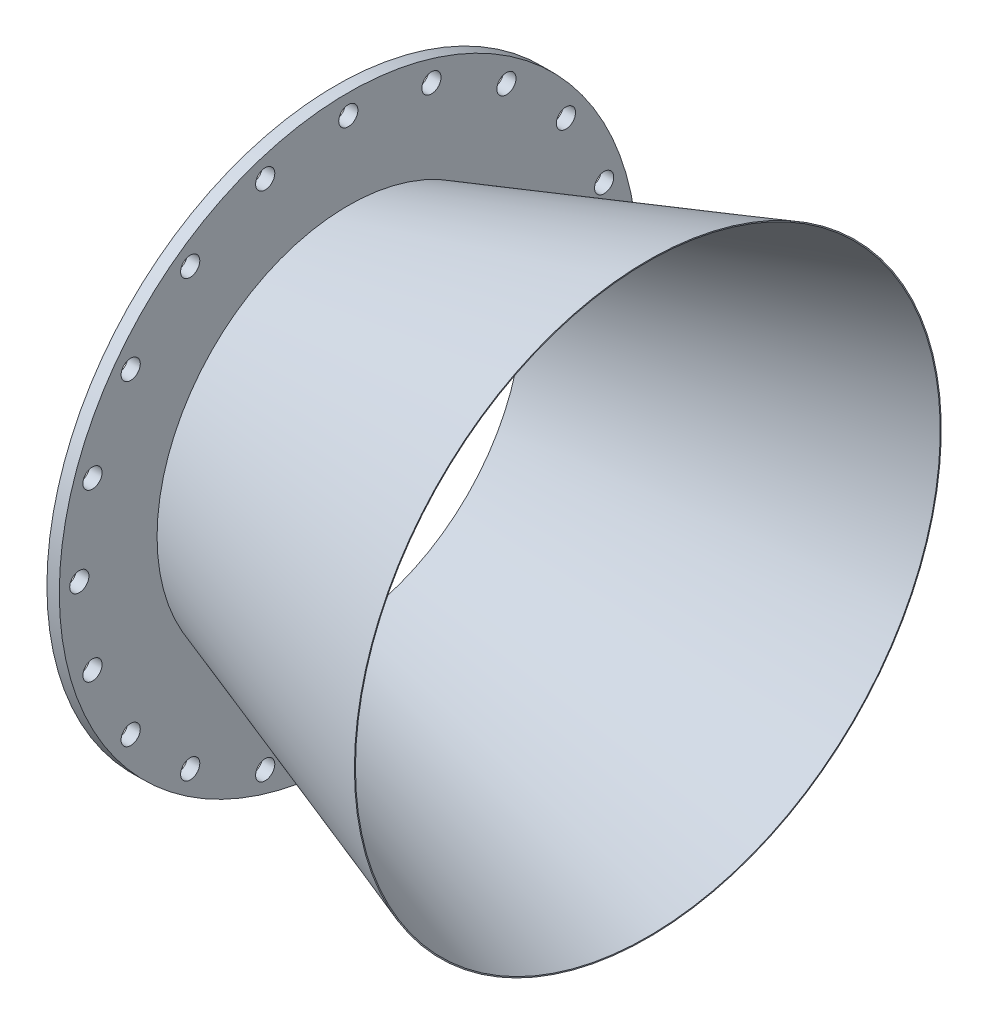
SolidWorks part; units mm, degrees
material "Tungsten"
ref_plane "Front Plane" through (0, 0, 0) normal (0, 0, 1) x (1, 0, 0)
ref_plane "Top Plane" through (0, 0, 0) normal (0, 1, 0) x (1, 0, 0)
ref_plane "Right Plane" through (0, 0, 0) normal (1, 0, 0) x (0, 0, -1)
sketch "Sketch1" plane through (0, 0, 0) normal (0, 0, 1) x (1, 0, 0)
  line L0 (0, 0) -> (0, 47.6758) construction
  line L1 (0, 0) -> (79.9592, 0) construction
  line L2 (79.9592, 0) -> (79.9592, 74.9554) construction
  line L3 (0, 47.6758) -> (45.8899, 47.6758) construction
  line L4 (0, 47.6758) -> (62.4191, 65.9935) construction
  line L5 (79.9592, 74.9554) -> (173.3924, 74.9554) construction
  line L6 (79.9592, 74.9554) -> (185.7919, 93.6166) construction
  line L10 (0, 47.6758) -> (79.9592, 74.9554)
  line L11 (0, 47.9442) -> (79.9592, 75.2238)
  line L12 (79.9592, 74.9554) -> (79.9592, 75.2238)
  line L13 (0, 47.6758) -> (0, 47.9442)
  line L14 (-0.082, 47.9162) -> (79.8772, 75.1958) construction
  dimension "D1" = 79.9592
  dimension "D2" = 47.6758
  dimension "D3" = 74.9554
  dimension "D4" = 16.355
  dimension "D5" = 10
  dimension "D6" = 0.254
revolve "Revolve1" add sketch "Sketch1" angle 360 about L1
sketch "Sketch3" plane through (0, 0, 0) normal (0, 0, 1) x (1, 0, 0)
  line L0 (79.9592, 75.2238) -> (0, 47.9442) construction
  line L1 (0, 47.9442) -> (3.175, 49.0274)
  line L2 (3.175, 49.0274) -> (3.175, 74.0918)
  line L3 (3.175, 74.0918) -> (0, 74.0918)
  line L4 (0, 74.0918) -> (0, 47.9442)
  line L5 (0, 0) -> (50000, 0) construction
  line L6 (0, 47.9442) -> (0, -47.9442) construction
  point P12 (0, 0)
  dimension "D1" = 3.175
  dimension "D2" = 74.0918
revolve "Revolve2" add sketch "Sketch3" angle 360 about L5
sketch "Sketch4" plane through (0, 0, 0) normal (-1, 0, 0) x (0, 0, 1)
  line L0 (0, 0) -> (0, 68.961) construction
  line L1 (-95.5286, 68.961) -> (95.5286, 68.961) construction
  point P6 (0, 68.961)
  dimension "D1" = 68.961
hole_wizard "#10 (0.1935) Diameter Hole1" positions "Sketch5" profile "Sketch6" hole size "#10" standard "ANSI Inch" end condition up to next
sketch "Sketch5" plane through (0, 0, 0) normal (-1, 0, 0) x (0, 0, 1)
  point P0 (0, 68.961)
sketch "Sketch6" plane through (0, 68.961, 0) normal (0, 1, 0) x (0, 0, 1)
  line L0 (0, 0) -> (0, 3.175)
  line L1 (0, 3.175) -> (2.4574, 3.175)
  line L2 (2.4574, 3.175) -> (2.4574, 0)
  line L5 (2.4574, 0) -> (0, 0)
  line L11 (0, -6.35) -> (0, 107.95) construction
  dimension "Thru Hole Dia." = 4.9149
  dimension "Thru Hole Depth" = 3.175
pattern_circular "CirPattern1" count 20 over 360 about axis through (79.9592, 0, 0) along (-1, 0, 0) of "#10 (0.1935) Diameter Hole1"
